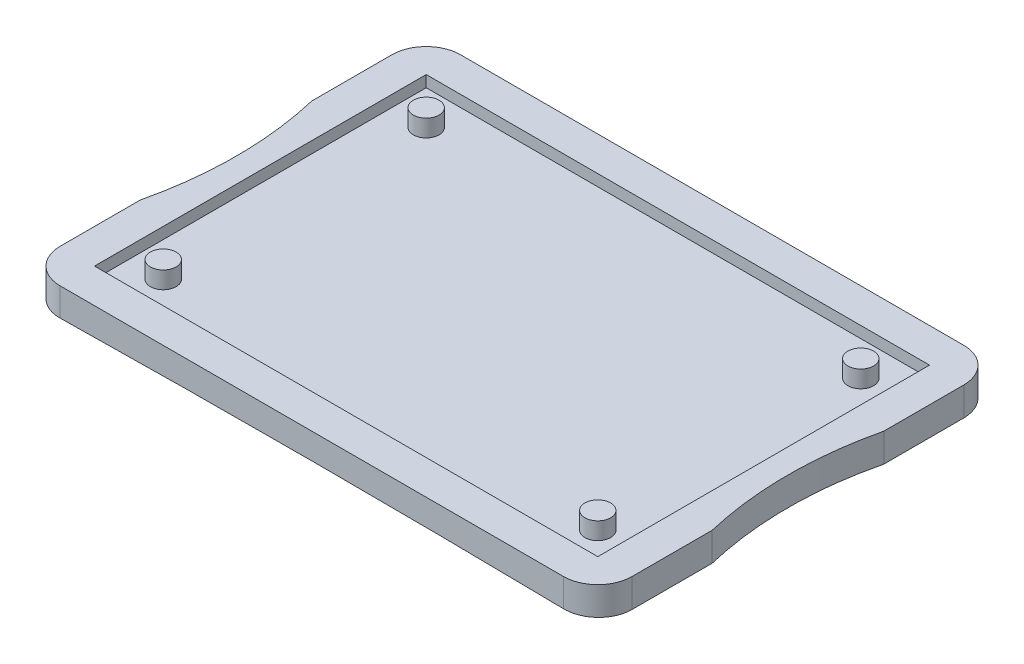
SolidWorks part; units mm, degrees
ref_plane "Front Plane" through (0, 0, 0) normal (0, 0, 1) x (1, 0, 0)
ref_plane "Top Plane" through (0, 0, 0) normal (0, 1, 0) x (1, 0, 0)
ref_plane "Right Plane" through (0, 0, 0) normal (1, 0, 0) x (0, 0, -1)
sketch "Sketch1" plane through (0, 0, 0) normal (0, 1, 0) x (1, 0, 0)
  line L0 (0, 17.5) -> (0, -17.5) construction
  line L1 (-25, -17.5) -> (25, -17.5)
  line L2 (-25, -17.5) -> (-25, 17.5)
  line L3 (-25, 17.5) -> (25, 17.5)
  line L4 (25, -17.5) -> (25, 17.5)
  line L9 (-22, 17.5) -> (22, 17.5) construction
  line L10 (25, 14.5) -> (25, 7.5) construction
  line L11 (-22, -17.5) -> (-12, -17.5) construction
  arc A0 (-25, -7.5) -> (-25, 7.5) centre (-56.7302, 0) ccw
  arc A1 (25, -7.5) -> (25, 7.5) centre (56.7302, 0) cw
  arc A2 (-22, -17.5) -> (-25, -14.5) centre (-22, -14.5) cw
  arc A3 (-25, 14.5) -> (-22, 17.5) centre (-22, 14.5) cw
  arc A4 (25, 14.5) -> (22, 17.5) centre (22, 14.5) ccw
  arc A5 (22, -17.5) -> (25, -14.5) centre (22, -14.5) ccw
  spline S1 degree 3 poles (25, 7.5) (24.7088, 6.2677) (24.471, 5.0256) (24.1465, 2.5135) (24.0611, 1.2521) (24.0624, -1.2809) (24.1491, -2.5382) (24.4725, -5.0321) (24.7092, -6.2695) (25, -7.5) knots 0 0 0 0 0.25 0.25 0.5 0.5 0.75 0.75 1 1 1 1 construction
  point P4 (-24.1257, 0)
extrude "Boss-Extrude1" add sketch "Sketch1" against normal blind 2.5 contours L0 L3 L2 L1 | L3 L0 L1 L4 region at (12.3235, 0, 0) region at (-12.3235, 0, 0)
sketch "Sketch2" plane through (0, 0, 0) normal (0, 0, 1) x (1, 0, 0)
  line L1 (-25, -2.5) -> (25, -2.5)
  line L2 (-25, -2.5) -> (-25, 0) construction
  arc A0 (-25, -2.5) -> (25, -2.5) centre (0, -1252.375) cw
  point P3 (0, -2.25)
  dimension "D2" = 1250.125
  dimension "D1" = 2.25
extrude "Cut-Extrude1" cut sketch "Sketch2" against normal through all both and the other way through all
sketch "Sketch3" plane through (0, 0, 0) normal (0, 1, 0) x (1, 0, 0)
  line L0 (-25, 17.5) -> (-18.9948, 11.4948)
  line L1 (-25, 17.5) -> (25, 17.5)
  line L2 (-25, 17.5) -> (-25, -17.5)
  line L3 (-25, -17.5) -> (25, -17.5)
  line L4 (25, 17.5) -> (25, -17.5)
  line L5 (-25, 0) -> (25, 0) construction
  line L6 (0, -17.5) -> (0, 17.5) construction
  line L8 (-22, 14.5) -> (22, 14.5)
  line L9 (-22, 14.5) -> (-22, -14.5)
  line L10 (-22, -14.5) -> (22, -14.5)
  line L11 (22, 14.5) -> (22, -14.5)
  circle A0 centre (-18.9948, 11.4948) radius 1.125
  circle A1 centre (18.9948, 11.4948) radius 1.125
  circle A2 centre (18.9948, -11.4948) radius 1.125
  circle A3 centre (-18.9948, -11.4948) radius 1.125
  dimension "D1" = 2.25
  dimension "D2" = 4.25
  dimension "D3" = 45
extrude "Cut-Extrude2" cut sketch "Sketch3" against normal blind 1 contours A0 L9 L10 L11 L8 A1 A2 A3 region at (0, 0, 0)
extrude "Boss-Extrude2" add sketch "Sketch3<5>" along normal blind 0.5 contours A0 | A3 | A2 | A1 region at (-18.5765, 0, -12.5048) region at (18.9948, 0, -11.4948) region at (18.9948, 0, 11.4948) region at (-18.9948, 0, 11.4948)
sketch "Sketch3<5>" plane through (0, 0, 0) normal (0, 1, 0) x (1, 0, 0) same geometry as "Sketch3"
